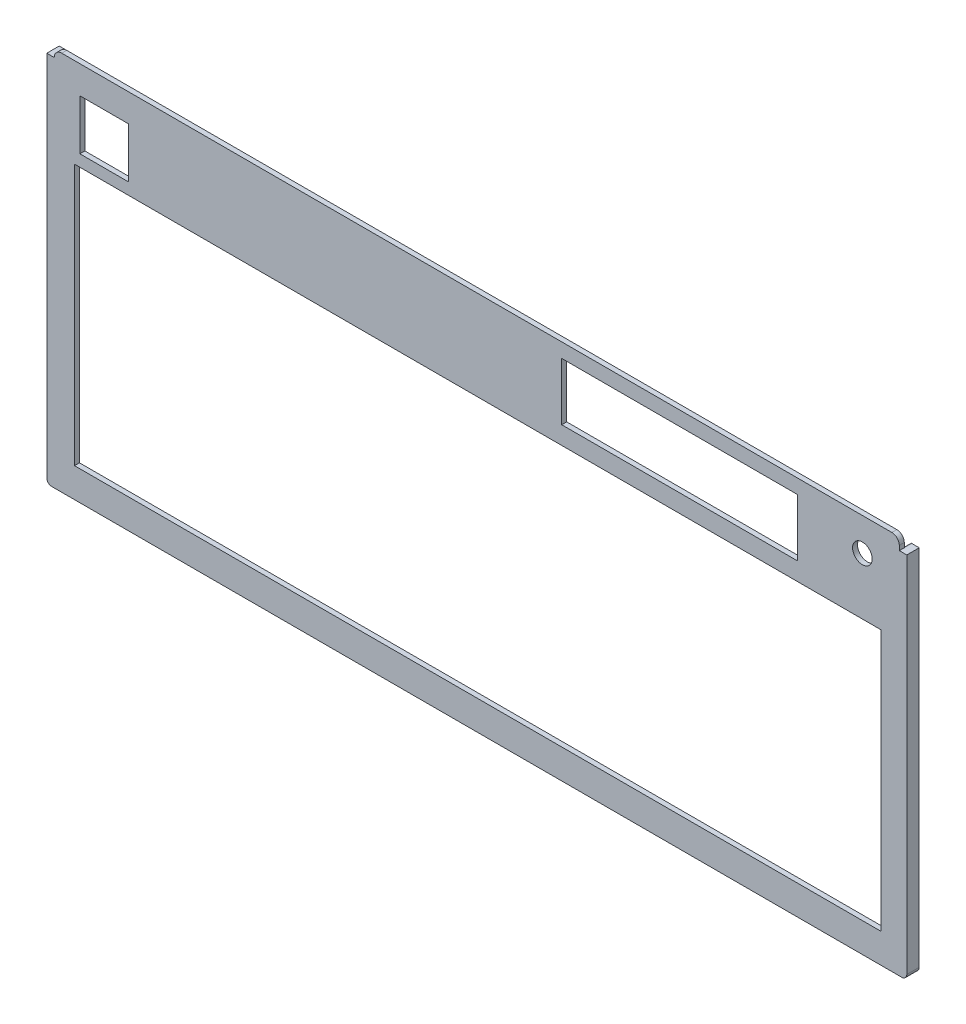
SolidWorks part; units mm, degrees
ref_plane "Front Plane" through (0, 0, 0) normal (0, 0, 1) x (1, 0, 0)
ref_plane "Top Plane" through (0, 0, 0) normal (0, 1, 0) x (1, 0, 0)
ref_plane "Right Plane" through (0, 0, 0) normal (1, 0, 0) x (0, 0, -1)
sketch "Sketch1" plane through (0, 0, 0) normal (0, 0, 1) x (1, 0, 0)
  line L0 (-65.3452, 80.1382) -> (268.63, 80.1382)
  line L6 (268.63, -69.8367) -> (-65.3452, -69.8367)
  line L7 (-68.3452, -66.8367) -> (-68.3452, 77.1382)
  line L10 (271.63, -66.8367) -> (271.63, 77.1382)
  line L13 (-58.0282, 68.9533) -> (-38.5345, 68.9533)
  line L14 (-58.0282, 68.9533) -> (-58.0282, 48.7377)
  line L15 (-58.0282, 48.7377) -> (-38.5345, 48.7377)
  line L16 (-38.5345, 68.9533) -> (-38.5345, 48.7377)
  line L17 (-60.1941, 44.0447) -> (264.3023, 44.0447)
  line L18 (-60.1941, 44.0447) -> (-60.1941, -61.0045)
  line L19 (-60.1941, -61.0045) -> (264.3023, -61.0045)
  line L20 (264.3023, 44.0447) -> (264.3023, -61.0045)
  line L21 (135.8256, 74.3682) -> (230.767, 74.3682)
  line L22 (135.8256, 74.3682) -> (135.8256, 51.2646)
  line L23 (135.8256, 51.2646) -> (230.767, 51.2646)
  line L24 (230.767, 74.3682) -> (230.767, 51.2646)
  arc A0 (-68.3452, 77.1382) -> (-65.3452, 80.1382) centre (-65.3452, 77.1382) cw
  arc A1 (268.63, 80.1382) -> (271.63, 77.1382) centre (268.63, 77.1382) cw
  arc A2 (268.63, -69.8367) -> (271.63, -66.8367) centre (268.63, -66.8367) ccw
  arc A3 (-65.3452, -69.8367) -> (-68.3452, -66.8367) centre (-65.3452, -66.8367) cw
  circle A4 centre (256.7754, 66.9302) radius 3.9489
  dimension "D1" = 3
  dimension "D2" = 3
extrude "Boss-Extrude1" add sketch "Sketch1" along normal blind 2
sketch "Sketch2" plane through (0, 0, 2) normal (0, 0, 1) x (1, 0, 0)
  line L0 (-68.3452, 77.1382) -> (-71.3373, 77.1382)
  line L1 (-71.3373, 77.1382) -> (-71.3373, -70.8494)
  line L2 (-69.3373, -72.8494) -> (272.6427, -72.8494)
  line L3 (274.6427, -70.8494) -> (274.6427, 75.3102)
  line L4 (274.6427, 75.3102) -> (271.6427, 75.3102)
  line L5 (271.6427, 75.3102) -> (271.6427, 77.1382) construction
  line L6 (274.6427, 75.3102) -> (271.6427, 75.3102) construction
  line L15 (-68.1452, 77.1382) -> (-68.1452, -66.8367)
  line L16 (-65.3452, -69.6367) -> (268.6303, -69.6367)
  line L17 (271.4303, -66.8369) -> (271.4427, 75.3102)
  line L18 (271.4427, 75.3102) -> (271.6427, 75.3102)
  line L20 (-68.3452, 77.1382) -> (-68.1452, 77.1382)
  arc A2 (-71.3373, -70.8494) -> (-69.3373, -72.8494) centre (-69.3373, -70.8494) ccw
  arc A3 (272.6427, -72.8494) -> (274.6427, -70.8494) centre (272.6427, -70.8494) ccw
  arc A4 (-68.1452, -66.8367) -> (-65.3452, -69.6367) centre (-65.3452, -66.8367) ccw
  arc A5 (268.6303, -69.6367) -> (271.4303, -66.8369) centre (268.6303, -66.8367) ccw
  dimension "D2" = 2
extrude "Boss-Extrude4" add sketch "Sketch2" against normal up to surface (5 mm away)
